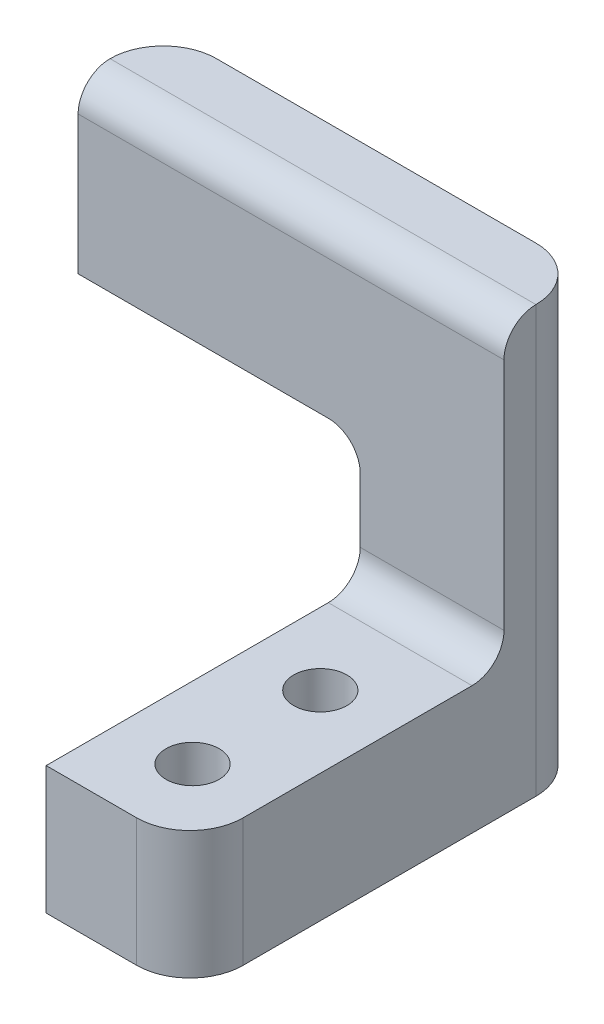
SolidWorks part; units mm, degrees
material "K110"
ref_plane "Front Plane" through (0, 0, 0) normal (0, 0, 1) x (1, 0, 0)
ref_plane "Top Plane" through (0, 0, 0) normal (0, 1, 0) x (1, 0, 0)
ref_plane "Right Plane" through (0, 0, 0) normal (1, 0, 0) x (0, 0, -1)
sketch "Sketch1" plane through (0, 0, 0) normal (0, 1, 0) x (1, 0, 0)
  line L1 (-20, -18.75) -> (20, -18.75)
  line L2 (-20, -18.75) -> (-20, 18.75)
  line L3 (-20, 18.75) -> (20, 18.75)
  line L4 (20, -18.75) -> (20, 18.75)
  line L5 (-20, -18.75) -> (20, 18.75) construction
  line L6 (-20, 18.75) -> (20, -18.75) construction
  point P0 (0, 0)
  dimension "D1" = 37.5
  dimension "D2" = 40
extrude "Boss-Extrude1" add sketch "Sketch1" against normal blind 40
sketch "Sketch2" plane through (20, 0, 0) normal (1, 0, 0) x (0, 0, -1)
  line L0 (18.75, -40) -> (18.75, 0) construction
  line L1 (-18.75, 0) -> (10.75, 0)
  line L2 (-18.75, 0) -> (-18.75, -28)
  line L3 (-18.75, -28) -> (10.75, -28)
  line L4 (10.75, 0) -> (10.75, -28)
  dimension "D1" = 8
  dimension "D2" = 28
extrude "Cut-Extrude1" cut sketch "Sketch2" against normal up to next
fillet "Fillet1" radius 3 2 edges at (0, 0, -10.75) (0, -28, -10.75)
hole_wizard "M6 Tapped Hole1" positions "Sketch12" profile "Sketch4" tap size "M6" standard "ISO" end condition through all
sketch "Sketch12" plane through (0, -40, 0) normal (0, -1, 0) x (-1, 0, 0)
  line L0 (-20, -18.75) -> (-20, 18.75) construction
  line L2 (20, -18.75) -> (-20, -18.75) construction
  point P0 (-13.25, -11.75)
  point P23 (-13.25, 0.25)
  dimension "D1" = 6.75
  dimension "D2" = 7
  dimension "D3" = 12
cosmetic thread "Hole Thread2" parameters "D2"=6
sketch "Sketch4" plane through (13.25, -40, 11.75) normal (1, 0, 0) x (0, 0, -1)
  line L0 (0, 0) -> (0, 40)
  line L1 (0, 40) -> (2.5, 40)
  line L2 (2.5, 40) -> (2.5, 0.525)
  line L3 (2.5, 0.525) -> (3.025, 0)
  line L5 (3.025, 0) -> (0, 0)
  line L6 (-2.5, 0.525) -> (-3.025, 0) construction
  line L11 (0, -6.35) -> (0, 107.95) construction
  dimension "Thru Tap Drill Dia." = 5
  dimension "Thru Tap Drill Depth" = 40
  dimension "Near C'Sink Dia." = 6.05
  dimension "Near C'Sink Angle" = 90
cosmetic thread "Hole Thread3" parameters "D2"=6
fillet "Fillet2" radius 5 4 edges at (20, -20, -18.75) (20, -34, 18.75) (-20, -34, 18.75) (-20, -20, -18.75)
sketch "Sketch7" plane through (0, 0, 0) normal (0, 1, 0) x (1, 0, 0)
  line L0 (-15, -18.75) -> (15, -18.75) construction
  line L1 (-6.5, -18.75) -> (6.5, -18.75)
  line L2 (-6.5, -18.75) -> (-6.5, 10.75)
  line L3 (-6.5, 10.75) -> (6.5, 10.75)
  line L4 (6.5, -18.75) -> (6.5, 10.75)
  line L6 (0, 7.75) -> (0, -18.75) construction
  line L7 (-20, 13.75) -> (20, 13.75) construction
  dimension "D1" = 3
  dimension "13" = 13
extrude "Cut-Extrude2" cut sketch "Sketch7" against normal up to next
sketch "Sketch8" plane through (0, 0, 0) normal (1, 0, 0) x (0, 0, -1)
  line L1 (-18.75, -40) -> (10.75, -40)
  line L2 (-18.75, -40) -> (-18.75, -3)
  line L3 (-18.75, -3) -> (10.75, -3)
  line L4 (10.75, -40) -> (10.75, -3)
extrude "Cut-Extrude3" cut sketch "Sketch8" against normal up to next
sketch "Sketch9" plane through (-20, 0, 0) normal (-1, 0, 0) x (0, 0, 1)
  line L0 (-10.75, -40) -> (-10.75, -3) construction
  line L1 (-18.75, -40) -> (-10.75, -40)
  line L2 (-18.75, -40) -> (-18.75, -16.0022)
  line L3 (-18.75, -16.0022) -> (-10.75, -16.0022)
  line L4 (-10.75, -40) -> (-10.75, -16.0022)
  line L5 (-23.7522, -28.0022) -> (-13.75, -28.0022) construction
  dimension "D1" = 12
extrude "Cut-Extrude4" cut sketch "Sketch9" against normal up to surface (26.5 mm away) up to face at (6.5, -32.3243, 1.5257)
fillet "Fillet5" radius 3 1 edges at (6.5, -16.0022, -14.75)
